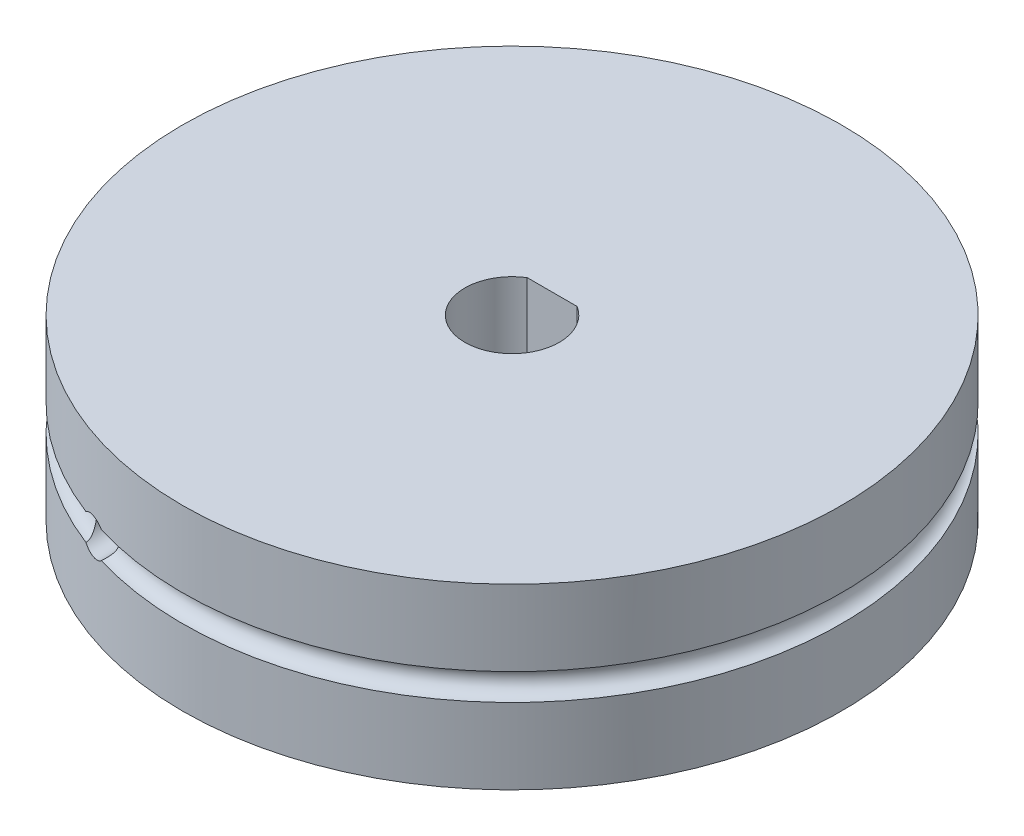
SolidWorks part; units mm, degrees
ref_plane "Front Plane" through (0, 0, 0) normal (0, 0, 1) x (1, 0, 0)
ref_plane "Top Plane" through (0, 0, 0) normal (0, 1, 0) x (1, 0, 0)
ref_plane "Right Plane" through (0, 0, 0) normal (1, 0, 0) x (0, 0, -1)
sketch "Sketch1" plane through (0, 0, 0) normal (0, 1, 0) x (1, 0, 0)
  circle A0 centre (0, 0) radius 18.5
  dimension "D1" = 37
extrude "Boss-Extrude1" add sketch "Sketch1" along normal blind 10
ref_axis "Axis1" through (0, 22.423, 0) along (0, -1, 0)
sketch "Sketch2" plane through (0, 0, 0) normal (0, 0, 1) x (1, 0, 0)
  line L1 (-18.5, 10) -> (-18.5, 0) construction
  circle A0 centre (-18.5, 5) radius 0.75
  point P2 (-18.5, 5)
  dimension "D1" = 1.5
revolve "Cut-Revolve1" cut sketch "Sketch2" angle 360 about axis through (0, 22.423, 0) along (0, -1, 0)
sketch "Sketch3" plane through (0, 10, 0) normal (0, 1, 0) x (1, 0, 0)
  line L0 (-1.4, 2.25) -> (1.4, 2.25)
  circle A0 centre (0, 0) radius 2.65
  point P5 (0, -2.65)
  dimension "D1" = 5.3
  dimension "D2" = 4.9
extrude "Cut-Extrude1" cut sketch "Sketch3" against normal up to next contours L0 A0 region at (0, 10, 0.0859)
sketch "Sketch4" plane through (0, 0, 0) normal (0, 0, 1) x (1, 0, 0)
  line L0 (-18.5, 5.75) -> (-18.5, 4.25) construction
  line L1 (0, 22.423) -> (0, 0) construction
  circle A0 centre (-6, 5) radius 1
  point P6 (-18.5, 5)
  dimension "D1" = 2
  dimension "D2" = 6
extrude "Cut-Extrude2" cut sketch "Sketch4" against normal up to next and the other way up to next
